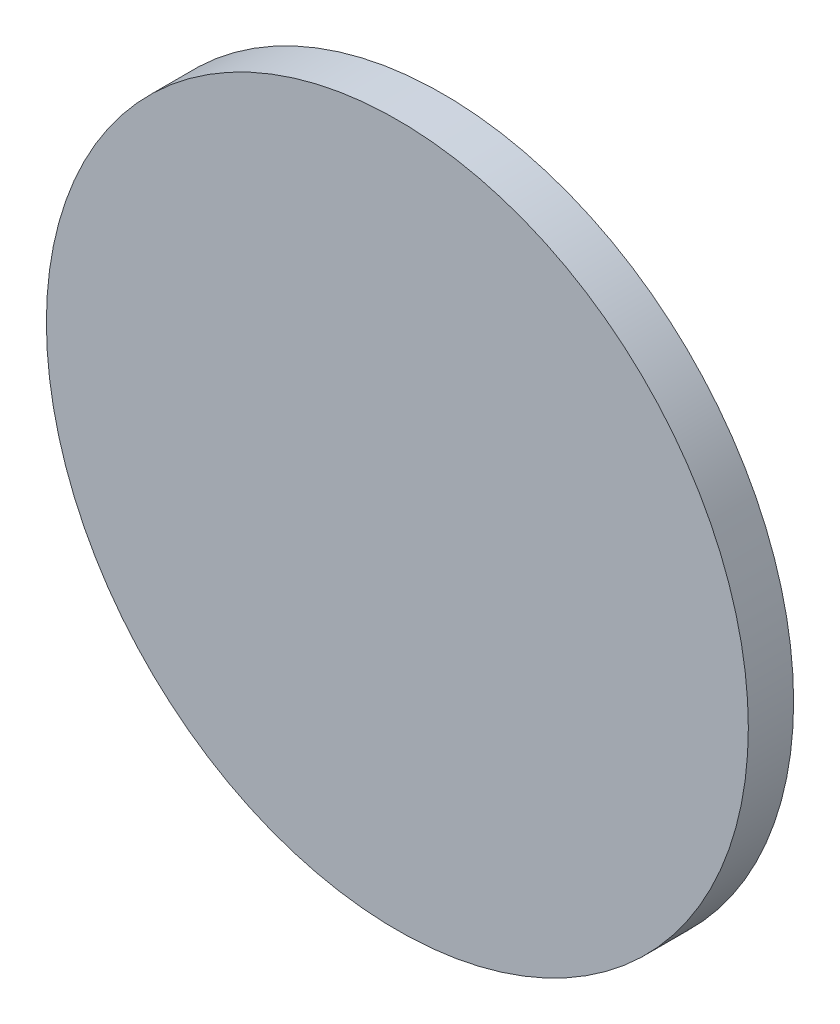
SolidWorks part; units mm, degrees
ref_plane "Front Plane" through (0, 0, 0) normal (0, 0, 1) x (1, 0, 0)
ref_plane "Top Plane" through (0, 0, 0) normal (0, 1, 0) x (1, 0, 0)
ref_plane "Right Plane" through (0, 0, 0) normal (1, 0, 0) x (0, 0, -1)
sketch "Sketch1" plane through (0, 0, 0) normal (0, 0, 1) x (1, 0, 0)
  circle A0 centre (0, 0) radius 15.5 construction
  circle A1 centre (0, 0) radius 15.5
extrude "Boss-Extrude1" add sketch "Sketch1" along normal blind 2
sketch "Sketch2" plane through (0, 0, 0) normal (0, 0, -1) x (-1, 0, 0)
  line L0 (-7.8174, 8.129) -> (-3.5527, 4.927)
  line L1 (0.2749, 6.0681) -> (2.0901, 11.0826)
  line L2 (-7.8774, 8.0491) -> (-3.6127, 4.8471)
  line L3 (0.3689, 6.0341) -> (2.1842, 11.0485)
  line L4 (-7.8774, 8.0491) -> (-3.6127, 4.8471) construction
  line L5 (0.3689, 6.0341) -> (2.1842, 11.0485) construction
  arc A0 (1.3416, 12.2836) -> (-7.8486, 9.5439) centre (0, 0) ccw
  arc A1 (-7.8486, 9.5439) -> (-7.8174, 8.129) centre (-7.277, 8.8488) ccw
  arc A2 (-3.5527, 4.927) -> (-2.5887, 4.8527) centre (-3.0123, 5.6468) ccw
  arc A3 (-0.491, 5.478) -> (-2.5887, 4.8527) centre (0, 0) ccw
  arc A4 (-0.491, 5.478) -> (0.2749, 6.0681) centre (-0.5714, 6.3744) ccw
  arc A5 (2.0901, 11.0826) -> (1.3416, 12.2836) centre (1.2439, 11.3889) ccw
  arc A6 (1.3524, 12.383) -> (-7.9122, 9.6211) centre (0, 0) ccw
  arc A7 (-7.9122, 9.6211) -> (-7.8774, 8.0491) centre (-7.277, 8.8488) ccw
  arc A8 (-3.6127, 4.8471) -> (-2.5416, 4.7645) centre (-3.0123, 5.6468) ccw
  arc A9 (-0.4821, 5.3784) -> (-2.5416, 4.7645) centre (0, 0) ccw
  arc A10 (-0.4821, 5.3784) -> (0.3689, 6.0341) centre (-0.5714, 6.3744) ccw
  arc A11 (2.1842, 11.0485) -> (1.3524, 12.383) centre (1.2439, 11.3889) ccw
  arc A12 (1.3524, 12.383) -> (-7.9122, 9.6211) centre (0, 0) ccw construction
  arc A13 (-7.9122, 9.6211) -> (-7.8774, 8.0491) centre (-7.277, 8.8488) ccw construction
  arc A14 (-3.6127, 4.8471) -> (-2.5416, 4.7645) centre (-3.0123, 5.6468) ccw construction
  arc A15 (-0.4821, 5.3784) -> (-2.5416, 4.7645) centre (0, 0) ccw construction
  arc A16 (-0.4821, 5.3784) -> (0.3689, 6.0341) centre (-0.5714, 6.3744) ccw construction
  arc A17 (2.1842, 11.0485) -> (1.3524, 12.383) centre (1.2439, 11.3889) ccw construction
  dimension "D1" = 0
  dimension "D2" = 0.1
extrude "Boss-Extrude2" add sketch "Sketch2" along normal offset from surface (1.9 mm away) 0.3
pattern_circular "CirPattern1" count 5 over 360 about axis through (0, 0, 2) along (0, 0, -1) of "Boss-Extrude2"
